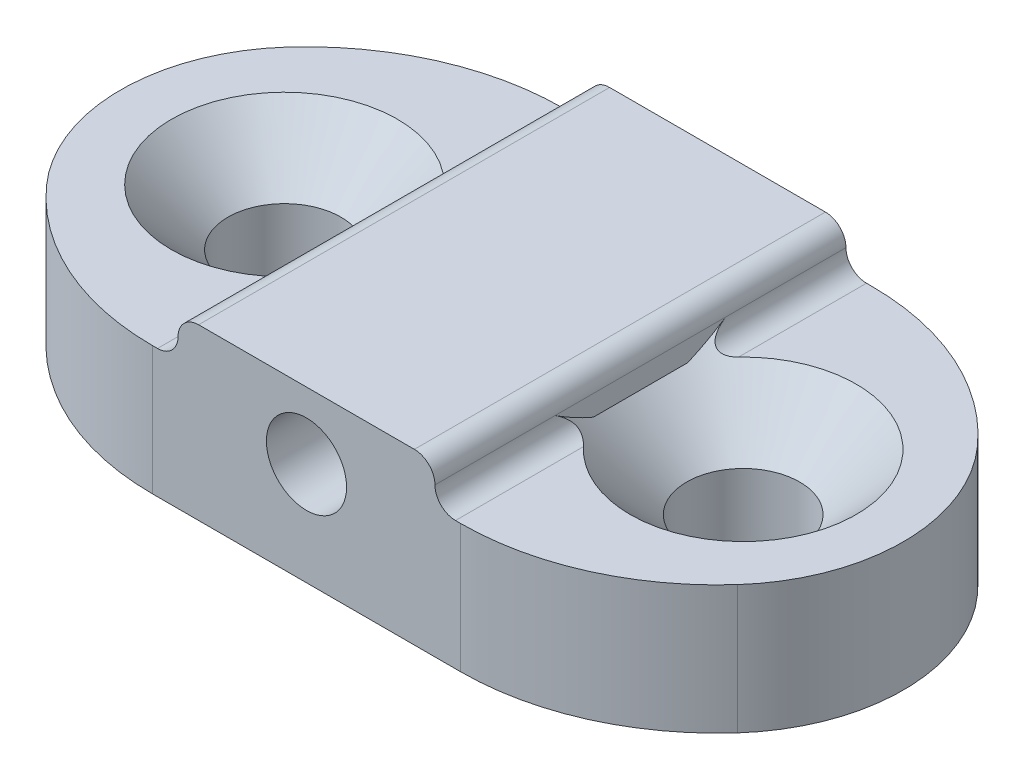
SolidWorks part; units mm, degrees
ref_plane "Front Plane" through (0, 0, 0) normal (0, 0, 1) x (1, 0, 0)
ref_plane "Top Plane" through (0, 0, 0) normal (0, 1, 0) x (1, 0, 0)
ref_plane "Right Plane" through (0, 0, 0) normal (1, 0, 0) x (0, 0, -1)
sketch "Sketch1" plane through (0, 0, 0) normal (0, 1, 0) x (1, 0, 0)
  line L1 (0, 0) -> (16, 0)
  line L2 (0, 0) -> (0, 8)
  line L3 (0, 8) -> (16, 8)
  line L4 (16, 0) -> (16, 8)
  dimension "D1" = 16
  dimension "D2" = 8
extrude "Boss-Extrude1" add sketch "Sketch1" along normal blind 2.5
sketch "Sketch2" plane through (0, 0, 0) normal (0, 0, 1) x (1, 0, 0)
  line L0 (0, 2.5) -> (16, 2.5) construction
  line L1 (5.5, 2.5) -> (10.5, 2.5)
  line L2 (5.5, 2.5) -> (5.5, 3.3)
  line L3 (5.5, 3.3) -> (10.5, 3.3)
  line L4 (10.5, 2.5) -> (10.5, 3.3)
  line L5 (8, 0) -> (8, 3.3) construction
  line L6 (0, 0) -> (16, 0) construction
  point P10 (8, 3.3)
  dimension "D1" = 0.8
  dimension "D2" = 5
extrude "Boss-Extrude2" add sketch "Sketch2" against normal up to surface (8 mm away) up to face at (8, 1.25, -8)
sketch "Sketch3" plane through (0, 0, 0) normal (0, 0, 1) x (1, 0, 0)
  line L0 (8, 3.3) -> (8, 0) construction
  line L1 (10.5, 3.3) -> (5.5, 3.3) construction
  line L2 (0, 0) -> (16, 0) construction
  circle A0 centre (8, 2) radius 0.78
  point P9 (8, 3.3)
  dimension "D1" = 1.56
  dimension "D2" = 2
extrude "Cut-Extrude1" cut sketch "Sketch3" against normal through all both and the other way through all
sketch "Sketch4" plane through (0, 2.5, 0) normal (0, 1, 0) x (1, 0, 0)
  line L0 (12.5, 8) -> (12.5, 4) construction
  line L1 (16, 8) -> (10.5, 8) construction
  line L2 (3.5, 8) -> (3.5, 4) construction
  line L3 (5.5, 8) -> (0, 8) construction
  line L4 (3.5, 4) -> (12.5, 4) construction
  line L5 (16, 0) -> (16, 8) construction
  line L6 (0, 8) -> (0, 0) construction
  point P12 (16, 4)
  dimension "D1" = 3.5
  dimension "D2" = 3.5
hole_wizard "CSK for M2 Countersunk Flat Head Screw1" positions "Sketch5" profile "Sketch6" countersink size "M2" standard "ISO" end condition through all
sketch "Sketch5" plane through (0, 2.5, 0) normal (0, 1, 0) x (1, 0, 0)
  point P0 (3.5711, 4)
  point P2 (12.5, 4)
sketch "Sketch6" plane through (3.5711, 2.5, -4) normal (1, 0, 0) x (0, 0, 1)
  line L0 (0, 0) -> (0, 2.5)
  line L1 (0, 2.5) -> (1.1, 2.5)
  line L2 (1.1, 2.5) -> (1.1, 1.1)
  line L3 (1.1, 1.1) -> (2.2, 0)
  line L5 (2.2, 0) -> (0, 0)
  line L6 (-1.1, 1.1) -> (-2.2, 0) construction
  line L11 (0, -6.35) -> (0, 107.95) construction
  dimension "Thru Hole Dia." = 2.2
  dimension "Thru Hole Depth" = 2.5
  dimension "Near C'Sink Dia." = 4.4
  dimension "Near C'Sink Angle" = 90
fillet "Fillet1" radius 0.4 6 edges at (10.5, 2.5, -6.4583) (10.5, 2.5, -1.5417) (10.5, 3.3, -4) (5.5, 3.3, -4) (5.5, 2.5, -1.471) (5.5, 2.5, -6.529)
fillet "Fillet2" radius 5 4 edges at (16, 1.25, 0) (16, 1.25, -8) (0, 1.25, -8) (0, 1.25, 0)
fillet "Fillet3" radius 3.5 2 edges at (0.101, 1.25, -4) (15.899, 1.25, -4)
